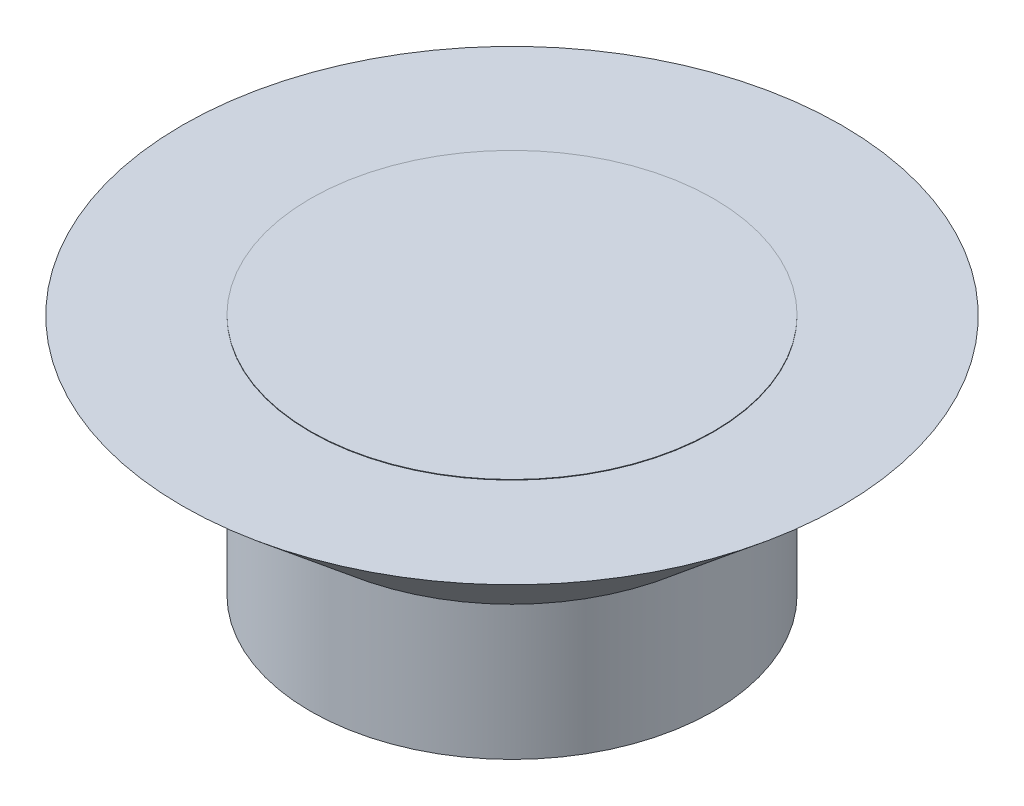
SolidWorks part; units mm, degrees
material "Custom Plastic"
ref_plane "Front Plane" through (0, 0, 0) normal (0, 0, 1) x (1, 0, 0)
ref_plane "Top Plane" through (0, 0, 0) normal (0, 1, 0) x (1, 0, 0)
ref_plane "Right Plane" through (0, 0, 0) normal (1, 0, 0) x (0, 0, -1)
sketch "Sketch1" plane through (0, 0, 0) normal (0, 0, 1) x (1, 0, 0)
  line L0 (0, 0) -> (0, 38.7866) construction
  line L1 (0, 0) -> (-9.525, 0)
  line L2 (-9.525, 0) -> (-9.525, 6.35)
  line L3 (-9.525, 6.35) -> (-15.5791, 11.43)
  line L4 (-15.5791, 11.43) -> (0, 11.43)
  line L5 (0, 11.43) -> (0, 0)
  dimension "D1" = 9.525
  dimension "D2" = 11.43
  dimension "D3" = 6.35
  dimension "D4" = 40
revolve "Revolve1" add sketch "Sketch1" angle 360 about L0
sketch "Sketch2" plane through (0, 11.43, 0) normal (0, 1, 0) x (1, 0, 0)
  circle A0 centre (0, 0) radius 9.525
  dimension "D1" = 19.05
extrude "Boss-Extrude1" add sketch "Sketch2" along normal blind 0.0254
